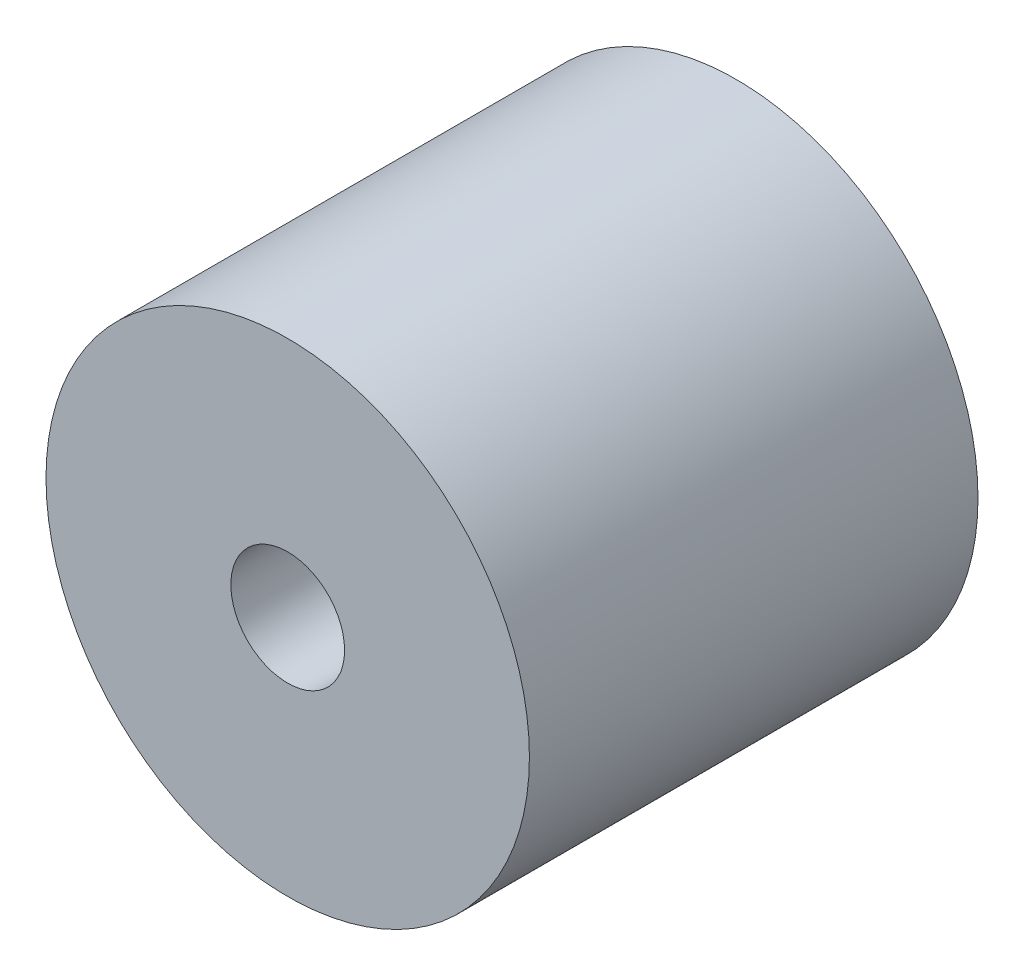
SolidWorks part; units mm, degrees
material "ABS"
ref_plane "Front" through (0, 0, 0) normal (0, 0, 1) x (1, 0, 0)
ref_plane "Top" through (0, 0, 0) normal (0, 1, 0) x (1, 0, 0)
ref_plane "Right" through (0, 0, 0) normal (1, 0, 0) x (0, 0, -1)
ref_axis "side-side" through (80.9, 0, 0) along (-1, 0, 0)
ref_axis "up-down" through (0, 50, 0) along (0, -1, 0)
ref_axis "front-back" through (0, 0, -80.9) along (0, 0, 1)
sketch "Sketch1" plane through (0, 0, 0) normal (0, 0, 1) x (1, 0, 0)
  circle A0 centre (0, 0) radius 34
  circle A1 centre (0, 0) radius 8
  dimension "D1" = 68
  dimension "D2" = 16
extrude "Boss-Extrude1" add sketch "Sketch1" along normal mid plane 63.1
shell "Shell1" thickness 3.5
